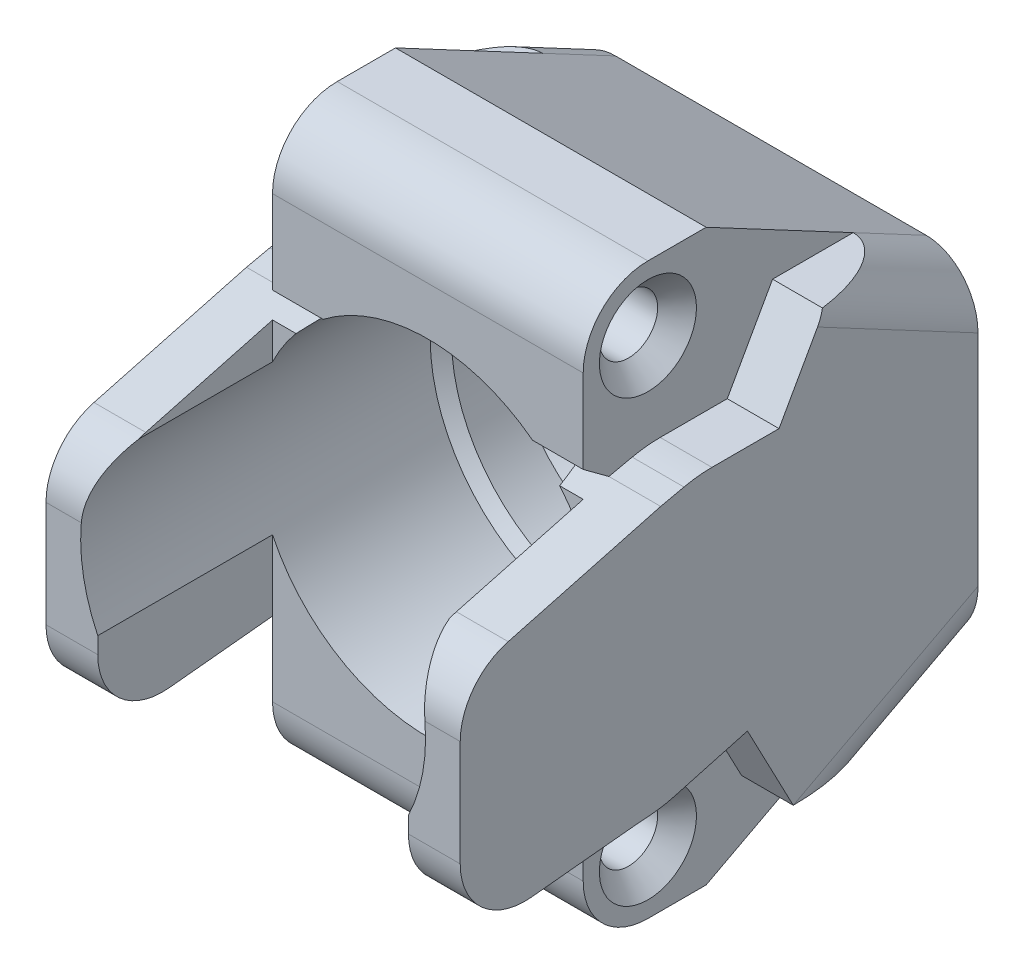
SolidWorks part; units mm, degrees
ref_plane "Front Plane" through (0, 0, 0) normal (0, 0, 1) x (1, 0, 0)
ref_plane "Top Plane" through (0, 0, 0) normal (0, 1, 0) x (1, 0, 0)
ref_plane "Right Plane" through (0, 0, 0) normal (1, 0, 0) x (0, 0, -1)
sketch "Sketch1" plane through (0, 0, 0) normal (1, 0, 0) x (0, 0, -1)
  line L0 (0, 13) -> (0, -13)
  line L1 (0, -13) -> (-17, -21.961)
  line L2 (-17, -21.961) -> (-21.5, -21.961)
  line L3 (-26.5, -16.961) -> (-26.5, -11.2272)
  line L4 (-26.5, -11.2272) -> (-34.5, -12.0312)
  line L5 (-40, -7.0563) -> (-40, 1.1324)
  line L6 (-36.2941, 5.962) -> (-24.5125, 9.1189)
  line L7 (-24.5125, 9.1189) -> (-26.5, 10.5845)
  line L8 (-26.5, 10.5845) -> (-26.5, 17.0391)
  line L9 (-21.5, 22.0391) -> (-17, 22.0391)
  line L10 (-17, 22.0391) -> (0, 13)
  arc A0 (-21.5, -21.961) -> (-26.5, -16.961) centre (-21.5, -16.961) cw
  arc A1 (-34.5, -12.0312) -> (-40, -7.0563) centre (-35, -7.0563) cw
  arc A2 (-40, 1.1324) -> (-36.2941, 5.962) centre (-35, 1.1324) cw
  arc A3 (-26.5, 17.0391) -> (-21.5, 22.0391) centre (-21.5, 17.0391) cw
  point P32 (5.5754, -8.6166)
  dimension "D4" = 5
  dimension "D8" = 8.1887
  dimension "D1" = 26
  dimension "D2" = 17
  dimension "D3" = 4.5
  dimension "D5" = 6.4545
  dimension "D6" = 2.4695
  dimension "D7" = 12.1972
  dimension "D9" = 8
  dimension "D10" = 5.7338
  dimension "D11" = 4.5
  dimension "D12" = 118
  dimension "D13" = 51.405
  dimension "D14" = 105
extrude "Boss-Extrude1" add sketch "Sketch1" along normal mid plane 32
sketch "Sketch2" plane through (0, 0, 0) normal (0, 0, -1) x (-1, 0, 0)
  line L5 (17.6, 0) -> (-17.6, 0) construction
  line L6 (-16, 22.0391) -> (-12, 22.0391)
  line L7 (16, 16) -> (16, 22.0391)
  line L8 (16, 22.0391) -> (12, 22.0391)
  line L9 (-16, 22.0391) -> (16, 22.0391) construction
  line L10 (12, 22.0391) -> (12, 16)
  line L11 (12, 16) -> (16, 16)
  line L12 (-16, 22.0391) -> (-16, 16)
  line L13 (-16, 16) -> (-12, 16)
  line L14 (-12, 22.0391) -> (-12, 16)
  line L15 (12, -16) -> (16, -16)
  line L16 (12, -22.0391) -> (12, -16)
  line L17 (16, -22.0391) -> (12, -22.0391)
  line L18 (16, -16) -> (16, -22.0391)
  line L19 (-16, -16) -> (-12, -16)
  line L20 (-12, -22.0391) -> (-12, -16)
  line L21 (-16, -22.0391) -> (-12, -22.0391)
  line L22 (-16, -22.0391) -> (-16, -16)
  dimension "D1" = 16
  dimension "D2" = 4
  dimension "D3" = 4
extrude "Cut-Extrude1" cut sketch "Sketch2" against normal through all
fillet "Fillet1" radius 4 4 edges at (16, -14.5, 2.8457) (-16, -14.5, 2.8457) (16, 14.5, 2.8211) (-16, 14.5, 2.8211)
sketch "Sketch3" plane through (-16, 0, 0) normal (-1, 0, 0) x (0, 0, 1)
  line L0 (14.2695, -16) -> (17.8101, -9.2566)
  line L1 (11.8703, 16) -> (15.3703, 9.7531)
  line L2 (15.3703, 9.7531) -> (20.5537, 9.7531)
  line L3 (22.7146, 9.5168) -> (24.5125, 9.1189)
  line L4 (24.5125, 9.1189) -> (26.5, 10.5845)
  line L5 (26.5, 10.5845) -> (26.5, 16)
  line L6 (26.5, 16) -> (11.8703, 16)
  line L7 (17.8101, -9.2566) -> (23.4559, -10.8058)
  line L8 (25.2952, -11.1297) -> (26.5, -11.2272)
  line L10 (14.2695, -16) -> (26.5, -16)
  line L11 (26.5, -16) -> (26.5, -11.2272)
  arc A0 (20.5537, 9.7531) -> (22.7146, 9.5168) centre (20.5537, -0.2469) cw
  arc A1 (23.4559, -10.8058) -> (25.2952, -11.1297) centre (26.1021, -1.1623) ccw
  dimension "D4" = 10
  dimension "D9" = 10
  dimension "D1" = 119.261
  dimension "D2" = 3.5
  dimension "D3" = 5.1835
  dimension "D5" = 1.8414
  dimension "D6" = 167.521
  dimension "D7" = 7.6164
  dimension "D8" = 5.8544
  dimension "D10" = 169.283
  dimension "D11" = 102.357
extrude "Cut-Extrude2" cut sketch "Sketch3" against normal blind 4
mirror "Mirror1" about plane through (0, 0, 0) normal (1, 0, 0) of "Cut-Extrude2"
sketch "Sketch4" plane through (0, 0, 0) normal (0, 0, -1) x (-1, 0, 0)
  circle A0 centre (0, 0) radius 12.5
  dimension "D1" = 25
extrude "Cut-Extrude3" cut sketch "Sketch4" against normal blind 5
sketch "Sketch5" plane through (0, 0, 5) normal (0, 0, -1) x (-1, 0, 0)
  circle A0 centre (0, 0) radius 11.435
  dimension "D1" = 22.87
extrude "Cut-Extrude4" cut sketch "Sketch5" against normal through all
sketch "Sketch7" plane through (0, 0, 5) normal (0, 0, -1) x (-1, 0, 0)
  circle A0 centre (0, 0) radius 12.5
extrude "Cut-Extrude5" cut sketch "Sketch7" against normal through all from offset 2 offset against normal yes
sketch "Sketch8" plane through (0, 0, 7) normal (0, 0, 1) x (1, 0, 0)
  circle A0 centre (0, 0) radius 13.322
  dimension "D1" = 26.644
extrude "Cut-Extrude6" cut sketch "Sketch8" along normal through all from offset 5
chamfer "Chamfer5" distance 1 3 edges at (0, 12.5, 7) (0, 12.5, 5) (13.322, 0, 12)
ref_plane "Plane1" through (0, 17.0391, 0) normal (0, 1, 0) x (-1, 0, 0)
sketch "Sketch9" plane through (0, 17.0391, 0) normal (0, 1, 0) x (-1, 0, 0)
  line L0 (-12, 26.5) -> (12, 26.5)
  line L1 (-12, 26.5) -> (-12, 21.5) construction
  line L2 (-12, 26.5) -> (12, 26.5) construction
  line L3 (12, 26.5) -> (12, 46.5)
  line L4 (12, 46.5) -> (-12, 46.5)
  line L5 (-12, 46.5) -> (-12, 26.5)
  line L6 (12, 15.3703) -> (12, 20.5537) construction
  dimension "D1" = 20
extrude "Cut-Extrude7" cut sketch "Sketch9" against normal through all
hole_wizard "CSK for M4 SFHCS1" positions "Sketch10" profile "Sketch11" countersink size "M4" standard "ANSI Metric" end condition through all
sketch "Sketch10" plane through (12, 0, 0) normal (1, 0, 0) x (0, 0, -1)
  point P0 (-21.5, 17.0391)
  point P3 (-21.5, -16.961)
sketch "Sketch11" plane through (12, 17.0391, 21.5) normal (0, 1, 0) x (0, 0, -1)
  line L0 (0, 0) -> (0, 28)
  line L1 (0, 28) -> (2.25, 28)
  line L2 (2.25, 28) -> (2.25, 1.5)
  line L3 (2.25, 1.5) -> (3.75, 0)
  line L5 (3.75, 0) -> (0, 0)
  line L6 (-2.25, 1.5) -> (-3.75, 0) construction
  line L11 (0, -6.35) -> (0, 107.95) construction
  dimension "Thru Hole Dia." = 4.5
  dimension "Thru Hole Depth" = 28
  dimension "Near C'Sink Dia." = 7.5
  dimension "Near C'Sink Angle" = 90
mirror "Mirror2" about plane through (0, 0, 0) normal (1, 0, 0) of "CSK for M4 SFHCS1"
